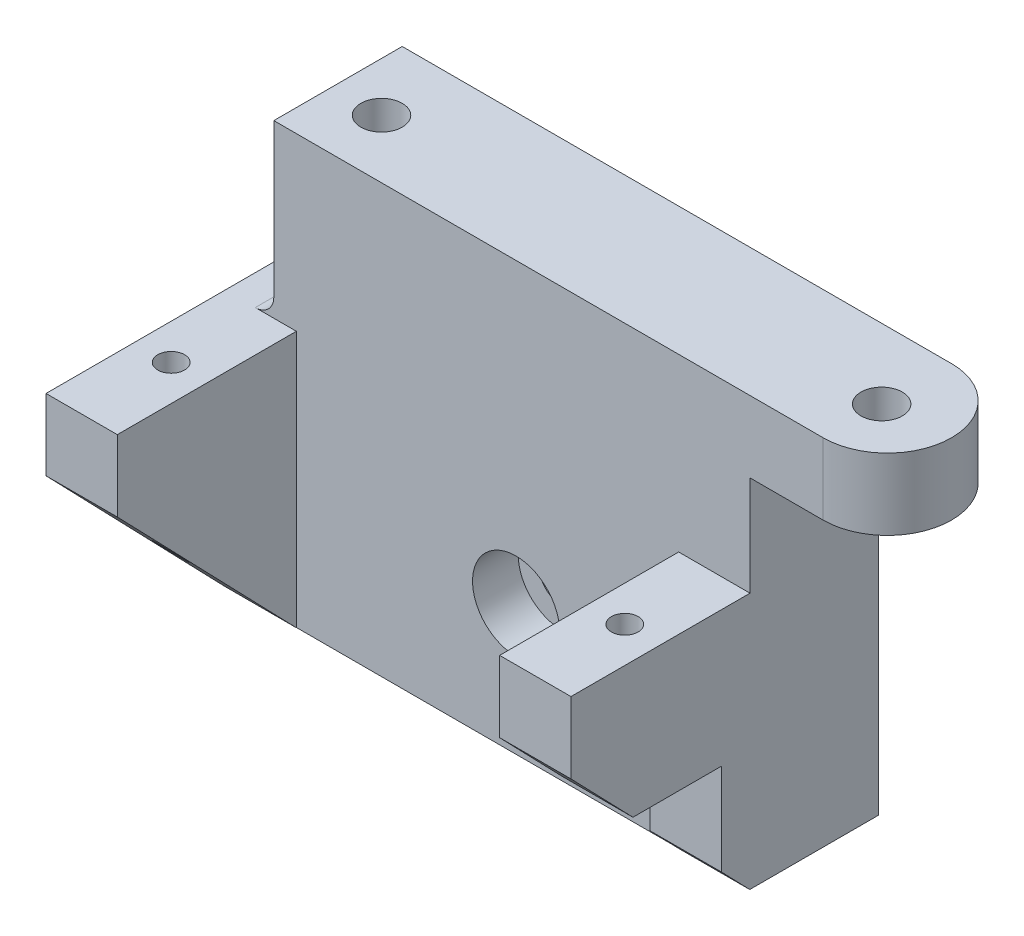
SolidWorks part; units mm, degrees
ref_plane "Front Plane" through (0, 0, 0) normal (0, 0, 1) x (1, 0, 0)
ref_plane "Top Plane" through (0, 0, 0) normal (0, 1, 0) x (1, 0, 0)
ref_plane "Right Plane" through (0, 0, 0) normal (1, 0, 0) x (0, 0, -1)
ref_plane "Model center" through (6, 0, 0) normal (1, 0, 0) x (0, 0, -1)
sketch "Sketch1" plane through (0, 0, 0) normal (0, 0, 1) x (1, 0, 0)
  line L0 (-4, 0) -> (4, 0)
  line L1 (-18.4, -8.9917) -> (18.4, -8.9917)
  line L2 (-18.4, -8.9917) -> (-18.4, 8.9917)
  line L3 (-18.4, 8.9917) -> (18.4, 8.9917)
  line L4 (18.4, -8.9917) -> (18.4, 8.9917)
  line L5 (-18.4, -8.9917) -> (18.4, 8.9917) construction
  line L6 (-18.4, 8.9917) -> (18.4, -8.9917) construction
  point P0 (0, 0)
  point P9 (0, 0)
  dimension "D1" = 8
  dimension "D2" = 36.8
extrude "Boss-Extrude1" add sketch "Sketch1" along normal blind 9 contours L1 L4 L3 L2 region at (-17.9904, 0, 0)
ref_plane "Plane1" through (0, 8.9917, 0) normal (0, 1, 0) x (1, 0, 0)
sketch "Sketch4" plane through (0, 8.9917, 0) normal (0, 1, 0) x (1, 0, 0)
  line L1 (0, 0) -> (0, -9) construction
  line L2 (-18.4, -9) -> (-13.4, -9)
  line L3 (-18.4, -9) -> (-18.4, -21.55)
  line L4 (-18.4, -21.55) -> (-13.4, -21.55)
  line L5 (-13.4, -9) -> (-13.4, -21.55)
  line L6 (-18.4, 0) -> (18.4, 0) construction
  line L7 (-18.4, -9) -> (18.4, -9) construction
  line L8 (13.4, -9) -> (13.4, -21.55)
  line L9 (18.4, -21.55) -> (13.4, -21.55)
  line L10 (18.4, -9) -> (18.4, -21.55)
  line L11 (18.4, -9) -> (13.4, -9)
  dimension "D1" = 5
  dimension "D2" = 12.55
extrude "Boss-Extrude2" add sketch "Sketch4" against normal blind 5
chamfer "Chamfer1" distance 12.55 distance2 13 2 edges at (-15.9, 3.9917, 9) (15.9, 3.9917, 9) first distance on face at (-15.9, 3.9917, 15.275) first distance on face at (15.9, 3.9917, 15.275)
sketch "Sketch2" plane through (0, 0, 0) normal (0, 0, -1) x (-1, 0, 0)
  line L0 (-10, 0) -> (-2, 0) construction
  circle A0 centre (-2, 0) radius 1.575
  circle A1 centre (-10, 0) radius 1.575
  point P12 (-6, 0)
  dimension "D2" = 3.15
  dimension "D1" = 8
  dimension "D3" = 6
extrude "Cut-Extrude1" cut sketch "Sketch2" against normal through all
sketch "Sketch3" plane through (0, 0, 9) normal (0, 0, 1) x (1, 0, 0)
  circle A0 centre (2, 0) radius 3.05
  circle A1 centre (10, 0) radius 3.05
  dimension "D1" = 6.1
extrude "Cut-Extrude2" cut sketch "Sketch3" against normal blind 3.2 and the other way through all
sketch "Sketch5" plane through (0, 8.9917, 0) normal (0, 1, 0) x (1, 0, 0)
  line L0 (0, 0) -> (0, -18.0516) construction
  line L1 (-18.4, 0) -> (18.4, 0) construction
  line L2 (-13.4, -15.275) -> (-18.4, -15.275) construction
  line L3 (-13.4, -21.55) -> (-13.4, -9) construction
  line L4 (-18.4, -21.55) -> (-18.4, 0) construction
  circle A0 centre (-15.9, -15.275) radius 0.9375
  circle A1 centre (15.9, -15.275) radius 0.9375
  dimension "D1" = 1.875
extrude "Cut-Extrude3" cut sketch "Sketch5" against normal up to surface (11.5 mm away) up to face at (-15.9, -2.5, 15.283)
sketch "Sketch6" plane through (0, 8.9917, 0) normal (0, 1, 0) x (1, 0, 0)
  line L0 (-13.4, -9) -> (13.4, -9) construction
  line L1 (-16.5, -9) -> (18.4, -9)
  line L2 (-16.5, -9) -> (-16.5, 0)
  line L3 (-16.5, 0) -> (18.4, 0)
  line L4 (18.4, -9) -> (18.4, 0)
  line L5 (-16.5, -9) -> (18.4, 0) construction
  line L6 (-16.5, 0) -> (18.4, -9) construction
  point P0 (0.95, -4.5)
extrude "Boss-Extrude3" add sketch "Sketch6" along normal blind 12
sketch "Sketch7" plane through (0, 0, 9) normal (0, 0, 1) x (1, 0, 0)
  line L0 (18.4, 3.9917) -> (18.4, -8.9917) construction
  line L1 (13.4, -5.5083) -> (18.4, -5.5083)
  line L2 (13.4, -5.5083) -> (13.4, -0.5083)
  line L3 (13.4, -0.5083) -> (18.4, -0.5083)
  line L4 (18.4, -5.5083) -> (18.4, -0.5083)
  line L5 (13.4, -5.5083) -> (18.4, -0.5083) construction
  line L6 (13.4, -0.5083) -> (18.4, -5.5083) construction
  line L7 (13.4, -8.9917) -> (13.4, 3.9917) construction
  line L8 (13.4, 8.9917) -> (18.4, 8.9917) construction
  line L9 (13.4, -5.5083) -> (13.4, -10.1043)
  line L10 (13.4, -10.1043) -> (18.4, -10.1043)
  line L11 (18.4, -10.1043) -> (18.4, -5.5083)
  point P0 (15.9, -3.0083)
  line M4 (13.4, -8.9917) -> (13.4, 8.9917)
  dimension "D1" = 5
  dimension "D2" = 12
extrude "Cut-Extrude4" cut sketch "Sketch7" along normal blind 8 from offset 2 contours L1 L4 L3 L2 M4 | L10 L11 L1 L9 M4 region at (15.9, -3.0083, 9) region at (15.9, -7.8063, 9)
sketch "Sketch8" plane through (0, 20.9917, 0) normal (0, 1, 0) x (1, 0, 0)
  line L1 (-16.5, -9) -> (18.4, -9) construction
  line L3 (6, -55) -> (6, 55) construction
  circle A0 centre (-11.53, -4.9) radius 1.45
  dimension "D1" = 2.9
  dimension "D2" = 4.1
  dimension "D3" = 17.53
extrude "Cut-Extrude5" cut sketch "Sketch8" against normal blind 10
sketch "Sketch9" plane through (0, 20.9917, 0) normal (0, 1, 0) x (1, 0, 0)
  line L0 (-11.53, -4.5) -> (-1.4412, -4.5) construction
  line L1 (-11.53, 0) -> (-1.4412, 0)
  line L2 (-11.53, -9) -> (-1.4412, -9)
  line L3 (-16.5, -9) -> (18.4, -9) construction
  line L4 (18.4, 0) -> (-16.5, 0) construction
  arc A0 (-11.53, 0) -> (-11.53, -9) centre (-11.53, -4.5) ccw
  arc A1 (-1.4412, -9) -> (-1.4412, 0) centre (-1.4412, -4.5) ccw
  circle A2 centre (-11.53, -4.9) radius 1.45 construction
  circle A3 centre (-11.53, -4.9) radius 1.45
  point P3 (-6.4856, -4.5)
extrude "Boss-Extrude4" add sketch "Sketch9" against normal blind 5
mirror "Mirror1" about plane through (6, 0, 0) normal (1, 0, 0) of "Boss-Extrude4", "Cut-Extrude5"
sketch "Sketch10" plane through (0, 0, 0) normal (0, 0, -1) x (-1, 0, 0)
  line L0 (16.5, 8.9917) -> (13.4, 8.9917) construction
  line L1 (16.5, 20.9917) -> (14.98, 20.9917)
  line L2 (16.5, 20.9917) -> (16.5, 8.9917)
  line L3 (16.5, 8.9917) -> (14.98, 8.9917)
  line L4 (14.98, 20.9917) -> (14.98, 8.9917)
  point P4 (0, 0)
  point P8 (0, 0)
  point P9 (0, 0)
  dimension "D1" = 2
extrude "Cut-Extrude6" cut sketch "Sketch10" against normal up to surface (9 mm away) up to face at (5.086, 9.195, 9)
fillet "Fillet1" radius 1.3 1 edges at (-14.98, 8.9917, 4.5)
